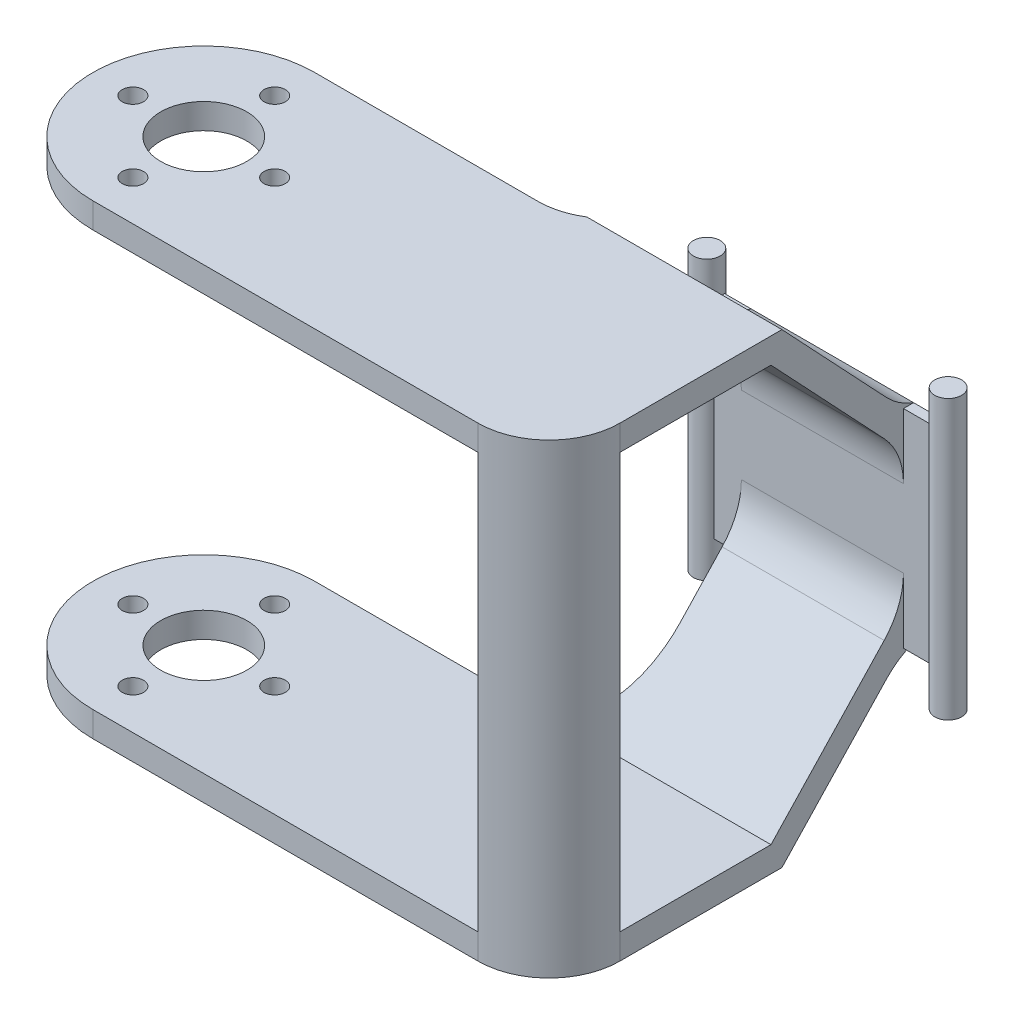
SolidWorks part; units mm, degrees
ref_plane "Front Plane" through (0, 0, 0) normal (0, 0, 1) x (1, 0, 0)
ref_plane "Top Plane" through (0, 0, 0) normal (0, 1, 0) x (1, 0, 0)
ref_plane "Right Plane" through (0, 0, 0) normal (1, 0, 0) x (0, 0, -1)
sketch "Sketch1" plane through (0, 0, 0) normal (0, 1, 0) x (1, 0, 0)
  line L1 (11.915, 0.5) -> (-11.915, 0.5)
  line L2 (11.915, 0.5) -> (11.915, -0.5)
  line L3 (11.915, -0.5) -> (-11.915, -0.5)
  line L4 (-11.915, 0.5) -> (-11.915, -0.5)
  line L5 (11.915, 0.5) -> (-11.915, -0.5) construction
  line L6 (11.915, -0.5) -> (-11.915, 0.5) construction
  point P0 (0, 0)
  dimension "D1" = 23.83
  dimension "D3" = 1
extrude "Boss-Extrude1" add sketch "Sketch1" along normal blind 20.5
ref_plane "Plane1" through (0, 10.25, 0) normal (0, 1, 0) x (1, 0, 0)
sketch "Sketch2" plane through (0, 10.25, 0) normal (0, 1, 0) x (1, 0, 0)
  line L0 (11.915, -0.5) -> (11.915, 0.5) construction
  line L1 (-11.915, 0.5) -> (-11.915, -0.5) construction
  line L2 (11.915, -0.5) -> (11.915, 0.5) construction
  line L3 (-11.915, 0.5) -> (-11.915, -0.5) construction
  circle A0 centre (-11.915, 0) radius 1.325
  circle A1 centre (11.915, 0) radius 1.325
  dimension "D1" = 2.65
extrude "Boss-Extrude2" add sketch "Sketch2" along normal mid plane 27.5
sketch "Sketch3" plane through (0, 20.5, 0) normal (0, 1, 0) x (1, 0, 0)
  line L0 (-10.688, -0.5) -> (10.688, -0.5) construction
  line L1 (-7.5, -0.5) -> (7.5, -0.5)
  line L2 (-7.5, -0.5) -> (-7.5, -26.5)
  line L3 (-7.5, -26.5) -> (7.5, -26.5)
  line L4 (7.5, -0.5) -> (7.5, -26.5)
  line L5 (0, -1000) -> (0, 49000) construction
  line L6 (-7.5, -26.5) -> (-32.5, -26.5)
  line L7 (-7.5, -26.5) -> (-7.5, -3.5)
  line L8 (-7.5, -3.5) -> (-32.5, -3.5)
  line L9 (-32.5, -26.5) -> (-32.5, -3.5)
  line L11 (-4.5, -3.5) -> (4.5, -3.5)
  line L12 (4.5, -3.5) -> (4.5, -23.5)
  line L13 (-4.5, -23.5) -> (4.5, -23.5)
  line L14 (-10.5, -23.5) -> (-29.5, -23.5)
  line L16 (-10.5, -6.5) -> (-29.5, -6.5)
  line L18 (-29.5, -23.5) -> (-29.5, -6.5) construction
  line L19 (-10.5, -23.5) -> (-10.5, -6.5) construction
  line L20 (-4.5, -3.5) -> (-4.5, -23.5) construction
  line L21 (-4.5, -3.5) -> (-4.5, -6.5)
  line L22 (-4.5, -6.5) -> (-10.5, -6.5)
  line L23 (-4.5, -23.5) -> (-10.5, -23.5)
  line L24 (-18.5, -6.5) -> (-18.5, -23.5)
  circle A0 centre (-32.5, -15) radius 11.5
  circle A1 centre (-32.5, -15) radius 4.25
  circle A2 centre (-32.5, -15) radius 7 construction
  circle A3 centre (-32.5, -8) radius 1.05
  circle A4 centre (-25.5, -15) radius 1.05
  circle A5 centre (-32.5, -22) radius 1.05
  circle A6 centre (-39.5, -15) radius 1.05
  point P10 (0, -0.5)
  line M14 (-10.688, -0.5) -> (10.688, -0.5)
  dimension "D5" = 8.5
  dimension "D6" = 14
  dimension "D7" = 2.1
  dimension "D1" = 15
  dimension "D2" = 26
  dimension "D3" = 23
  dimension "D4" = 25
  dimension "D9" = 14
  dimension "D8" = 3
extrude "Boss-Extrude3" [suppressed] add sketch "Sketch3" against normal up to surface (18.5 mm away) contours L4 L2 L3 M14 | A0 L6 L2 L8 | A5 L9 A0 A3 A1 A4 | A5 L9 A1 A3 A0 A6 | A0 L16 L22 L2 L8 | A0 L6 L2 L23 L14
sketch "Sketch4" plane through (0, 0, 0) normal (1, 0, 0) x (0, 0, -1)
  line L0 (-0.5, 20.5) -> (-12.5, 33.25)
  line L1 (-12.5, 33.25) -> (-35.5, 33.25)
  line L2 (-35.5, 33.25) -> (-35.5, 30.75)
  line L3 (-35.5, 30.75) -> (-13.5802, 30.75)
  line L4 (-13.5802, 30.75) -> (-0.5, 16.8523)
  line L5 (-0.5, 20.5) -> (-0.5, 0) construction
  line L6 (-0.5, 20.5) -> (-0.5, 0)
  line L7 (-0.5, 0) -> (-12.5, -12.75)
  line L8 (-12.5, -12.75) -> (-35.5, -12.75)
  line L9 (-35.5, -12.75) -> (-35.5, -10.25)
  line L10 (-35.5, -10.25) -> (-13.5802, -10.25)
  line L11 (-13.5802, -10.25) -> (-0.5, 3.6477)
  line L12 (-1000.5, 10.25) -> (48999.5, 10.25) construction
  line L13 (-35.5, 30.75) -> (-35.5, -10.25) construction
  point P3 (-35.5, 10.25)
  point P20 (-0.5, 10.25)
  dimension "D1" = 2.5
  dimension "D2" = 41
  dimension "D3" = 23
  dimension "D4" = 2.5
  dimension "D5" = 35
  dimension "D6" = 2.5
extrude "Boss-Extrude4" add sketch "Sketch4" along normal mid plane 16 contours L6 L0 L1 L2 L3 L4 | L11 L10 L9 L8 L7 L6
sketch "Sketch5" plane through (-8, 0, 0) normal (-1, 0, 0) x (0, 0, 1)
  line L1 (35.5, 33.25) -> (13.5802, 33.25)
  line L2 (35.5, 33.25) -> (35.5, 30.75)
  line L3 (35.5, 30.75) -> (13.5802, 30.75)
  line L4 (13.5802, 33.25) -> (13.5802, 30.75)
  line L5 (35.5, -12.75) -> (13.5802, -12.75)
  line L6 (35.5, -12.75) -> (35.5, -10.25)
  line L7 (35.5, -10.25) -> (13.5802, -10.25)
  line L8 (13.5802, -12.75) -> (13.5802, -10.25)
extrude "Boss-Extrude5" add sketch "Sketch5" along normal blind 40
sketch "Sketch6" plane through (0, 33.25, 0) normal (0, 1, 0) x (1, 0, 0)
  line L0 (-37.0401, -13.5802) -> (-37.0401, -35.5) construction
  line L1 (-48, -13.5802) -> (-8, -13.5802) construction
  line L2 (8, -35.5) -> (-48, -35.5) construction
  line L3 (-48, -24.5401) -> (8, -24.5401) construction
  line L4 (-48, -35.5) -> (-48, -13.5802) construction
  line L5 (8, -12.5) -> (8, -35.5) construction
  line L6 (-37.0401, -13.5802) -> (-48, -13.5802)
  line L7 (-48, -13.5802) -> (-48, -35.5)
  line L8 (-48, -35.5) -> (-37.0401, -35.5)
  circle A0 centre (-37.0401, -24.5401) radius 10.9599
  circle A1 centre (-37.0401, -24.5401) radius 4.25
  circle A2 centre (-37.0401, -24.5401) radius 7 construction
  circle A3 centre (-37.0401, -17.5401) radius 1.05
  circle A4 centre (-30.0401, -24.5401) radius 1.05
  circle A5 centre (-37.0401, -31.5401) radius 1.05
  circle A6 centre (-44.0401, -24.5401) radius 1.05
  point P12 (-37.0401, -24.5401)
  line M9 (-8, -13.5802) -> (-48, -13.5802)
  line M10 (-48, -13.5802) -> (-48, -35.5)
  line M11 (-48, -35.5) -> (8, -35.5)
  dimension "D1" = 8.5
  dimension "D2" = 14
  dimension "D3" = 2.1
extrude "Cut-Extrude1" cut sketch "Sketch6" against normal through all contours A1 | A6 | A3 | A4 | A5 | A0 M9 M10 | A0 L7 M11
fillet "Fillet1" radius 7 4 edges at (-8, -11.5, 13.5802) (-8, 32, 13.5802) (8, -11.5, 35.5) (8, 32, 35.5)
fillet "Fillet2" radius 7 2 edges at (0, 3.6477, 0.5) (0, 16.8523, 0.5)
fillet "Fillet3" radius 7 2 edges at (0, 20.5, 0.5) (0, 0, 0.5)
sketch "Sketch8" plane through (0, -10.25, 0) normal (0, 1, 0) x (1, 0, 0)
  line L0 (-37.0401, -13.5802) -> (-15, -13.5802) construction
  line L1 (-37.0401, -13.5802) -> (-15, -13.5802)
  line L2 (8, -28.5) -> (5, -28.5)
  line L3 (1, -35.5) -> (1, -32.5)
  arc A0 (-15, -13.5802) -> (-8, -6.5802) centre (-15, -6.5802) ccw construction
  arc A1 (1, -35.5) -> (8, -28.5) centre (1, -28.5) ccw construction
  arc A2 (-15, -13.5802) -> (-8, -6.5802) centre (-15, -6.5802) ccw
  arc A3 (1, -35.5) -> (8, -28.5) centre (1, -28.5) ccw
  circle A4 centre (-1.5277, -25.9723) radius 7
  arc M10 (1, -35.5) -> (8, -28.5) centre (1, -28.5) ccw
  dimension "D1" = 3
extrude "Boss-Extrude6" add sketch "Sketch8" along normal up to surface (41 mm away) contours A4 L3 L2 M10 up to face at (-37.0401, 30.75, 28.7901)
equation "\"D4@Sketch4\"=\"D1@Sketch4\""
equation "\"D6@Sketch4\"=\"D1@Sketch4\""
